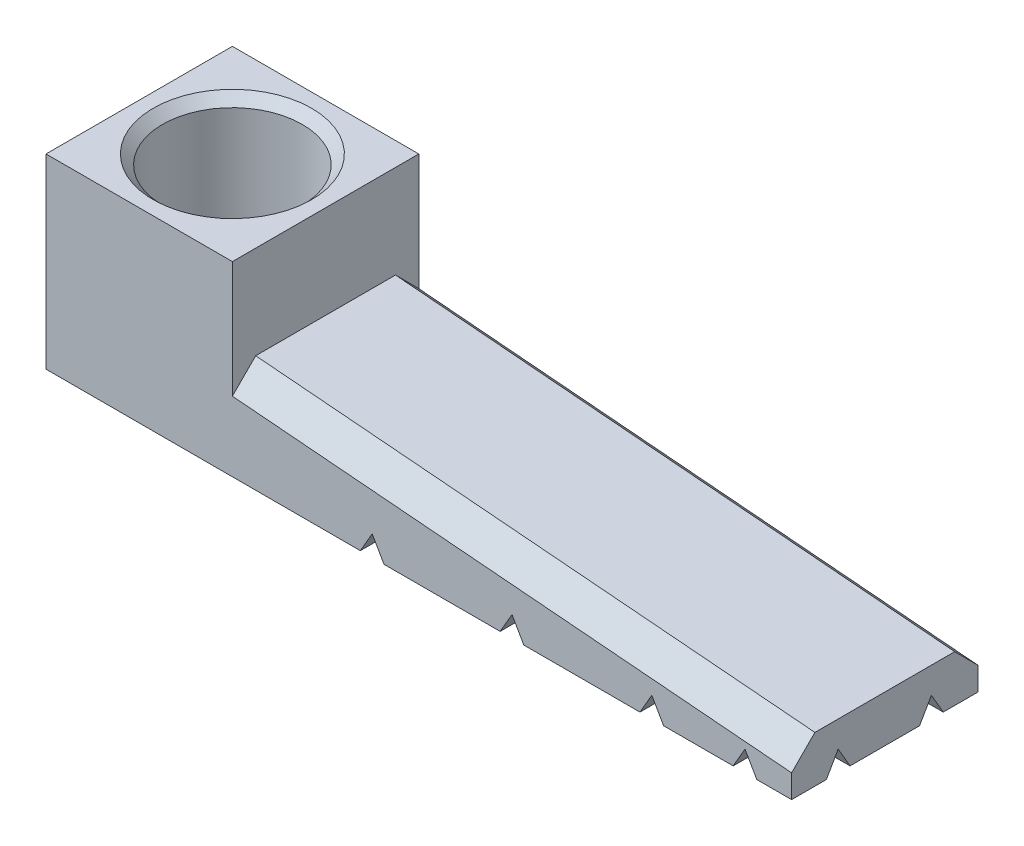
SolidWorks part; units mm, degrees
ref_plane "Front Plane" through (0, 0, 0) normal (0, 0, 1) x (1, 0, 0)
ref_plane "Top Plane" through (0, 0, 0) normal (0, 1, 0) x (1, 0, 0)
ref_plane "Right Plane" through (0, 0, 0) normal (1, 0, 0) x (0, 0, -1)
sketch "Sketch1" plane through (0, 0, 0) normal (0, 0, 1) x (1, 0, 0)
  line L0 (0, 0) -> (0, 20)
  line L1 (0, 20) -> (20, 20)
  line L2 (20, 20) -> (20, 10)
  line L3 (0, 0) -> (80, 0)
  line L4 (80, 0) -> (80, 5)
  line L5 (80, 5) -> (20, 10)
  dimension "D1" = 20
  dimension "D2" = 20
  dimension "D3" = 10
  dimension "D4" = 80
  dimension "D5" = 5
extrude "Boss-Extrude1" add sketch "Sketch1" along normal blind 20
chamfer "Chamfer1" distance 2.5 angle 45 2 edges at (50, 7.5, 0) (50, 7.5, 20)
ref_plane "Plane1" through (0, 0, 0) normal (0, -1, 0) x (-1, 0, 0)
sketch "Sketch2" plane through (0, 0, 0) normal (0, -1, 0) x (-1, 0, 0)
  line L0 (0, -10) -> (-20, -10) construction
  line L1 (0, -20) -> (0, 0) construction
  line L2 (-10, -1010) -> (-10, 48990) construction
  circle A0 centre (-10, -10) radius 7.5
  point P7 (-10, -10)
  dimension "D1" = 15
extrude "Cut-Extrude1" cut sketch "Sketch2" against normal through all
ref_plane "Plane2" through (80, 0, 0) normal (1, 0, 0) x (0, 0, -1)
sketch "Sketch3" plane through (80, 0, 0) normal (1, 0, 0) x (0, 0, -1)
  line L0 (-15, -997.6224) -> (-15, 49002.3776) construction
  line L2 (-5, -998.5989) -> (-5, 49001.4011) construction
  line L3 (0, 0) -> (0, 2.4913) construction
  line L4 (-20, 20) -> (-20, 0) construction
  line L5 (-20, 0) -> (0, 0) construction
  line L6 (-15, 2.1997) -> (-16.27, 0)
  line L7 (-16.27, 0) -> (-13.73, 0)
  line L8 (-13.73, 0) -> (-15, 2.1997)
  line L9 (-10, -995) -> (-10, 49005) construction
  line L10 (-20, 0) -> (-20, 2.4913) construction
  line L11 (-6.27, 0) -> (-5, 2.1997)
  line L12 (-3.73, 0) -> (-6.27, 0)
  line L13 (-5, 2.1997) -> (-3.73, 0)
  circle A0 centre (-15, 0.7332) radius 0.7332 construction
  circle A1 centre (-5, 0.7332) radius 0.7332 construction
  dimension "D3" = 2.54
  dimension "D1" = 5
  dimension "D2" = 5
  dimension "D4" = 10
extrude "Cut-Extrude2" cut sketch "Sketch3" against normal up to surface (60 mm away) up to face at (20, 12.4971, 10)
sketch "Sketch4" plane through (0, 0, 0) normal (0, 0, 1) x (1, 0, 0)
  line L0 (0, 0) -> (80, 0) construction
  line L1 (75, 2.1997) -> (73.73, 0)
  line L2 (73.73, 0) -> (76.27, 0)
  line L3 (76.27, 0) -> (75, 2.1997)
  line L4 (80, 0) -> (80, 2.4913) construction
  line L5 (65, 2.1997) -> (63.73, 0)
  line L6 (63.73, 0) -> (66.27, 0)
  line L7 (66.27, 0) -> (65, 2.1997)
  line L9 (50, 2.1997) -> (48.73, 0)
  line L10 (48.73, 0) -> (51.27, 0)
  line L11 (51.27, 0) -> (50, 2.1997)
  line L12 (35, 2.1997) -> (33.73, 0)
  line L13 (33.73, 0) -> (36.27, 0)
  line L14 (36.27, 0) -> (35, 2.1997)
  circle A0 centre (75, 0.7332) radius 0.7332 construction
  circle A1 centre (65, 0.7332) radius 0.7332 construction
  circle A2 centre (50, 0.7332) radius 0.7332 construction
  circle A3 centre (35, 0.7332) radius 0.7332 construction
  dimension "D1" = 2.54
  dimension "D2" = 5
  dimension "D3" = 2.54
  dimension "D4" = 15
  dimension "D5" = 2.54
  dimension "D6" = 2.54
  dimension "D7" = 30
  dimension "D8" = 45
extrude "Cut-Extrude3" cut sketch "Sketch4" along normal through all
chamfer "Chamfer2" distance 1 angle 45 2 edges at (10, 0, 2.5) (10, 20, 2.5)
